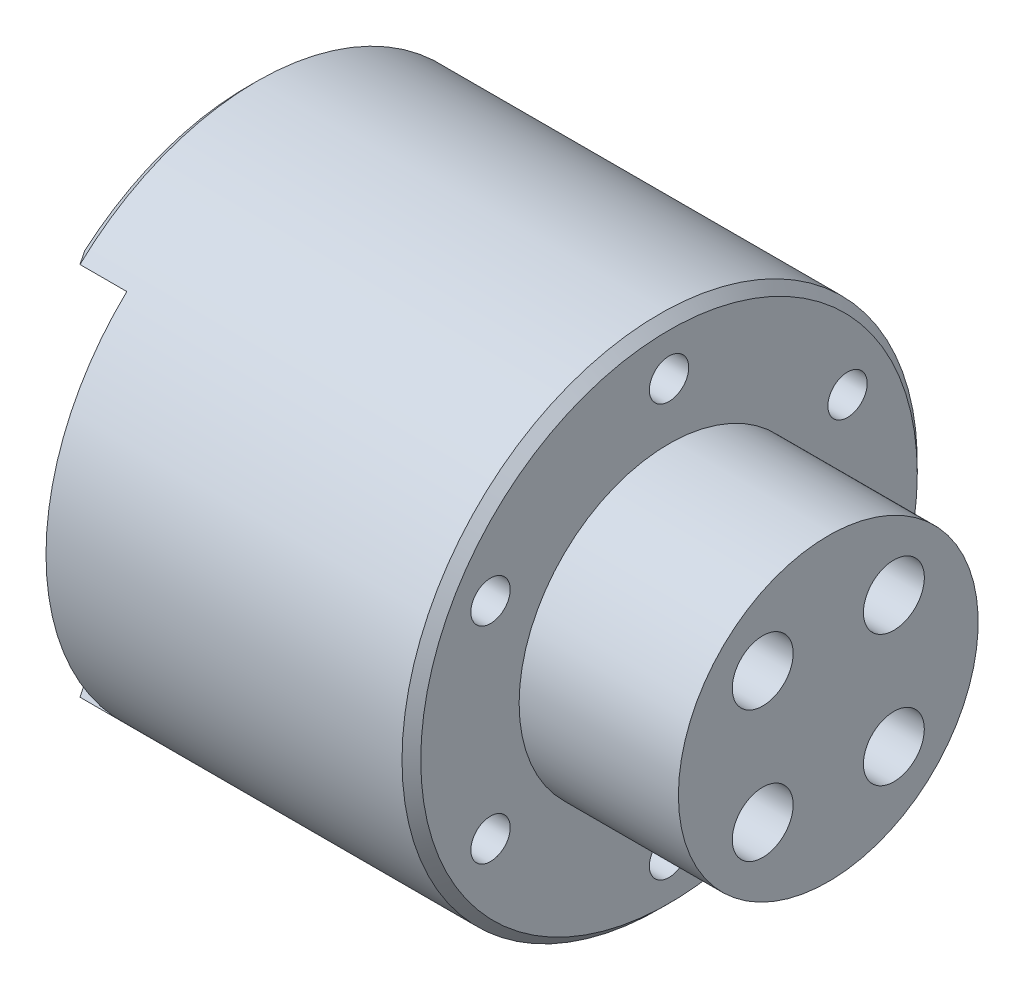
SolidWorks part; units mm, degrees
material "1023 Carbon Steel Sheet (SS)"
ref_plane "Front Plane" through (0, 0, 0) normal (0, 0, 1) x (1, 0, 0)
ref_plane "Top Plane" through (0, 0, 0) normal (0, 1, 0) x (1, 0, 0)
ref_plane "Right Plane" through (0, 0, 0) normal (1, 0, 0) x (0, 0, -1)
sketch "Sketch1" plane through (0, 0, 0) normal (0, 0, 1) x (1, 0, 0)
  line L0 (0, 0) -> (221.0251, 0) construction
  line L1 (55, 0) -> (-55, 0) construction
  line L2 (0, 0) -> (0, 27.5)
  line L3 (0, -55) -> (0, 55) construction
  line L4 (0, 27.5) -> (45, 27.5)
  line L13 (45, 27.5) -> (45, 16)
  line L14 (62, 0) -> (0, 0)
  line L15 (45, 16) -> (62, 16)
  line L16 (62, 16) -> (62, 0)
  dimension "D1" = 45
  dimension "D2" = 55
  dimension "D3" = 32
  dimension "D4" = 17
revolve "Revolve1" add sketch "Sketch1" angle 360 about L0
ref_axis "Axis1" through (45, 0, 0) along (-1, 0, 0)
sketch "Sketch2" plane through (0, 0, 0) normal (-1, 0, 0) x (0, 0, 1)
  line L0 (0, -18.7) -> (0, 18.7) construction
  line L1 (55, 0) -> (-55, 0) construction
  circle A0 centre (-7, 7) radius 3.25
  circle A1 centre (7, 7) radius 3.25
  circle A2 centre (7, -7) radius 3.25
  circle A3 centre (-7, -7) radius 3.25
  dimension "D3" = 6.5
  dimension "D1" = 14
  dimension "D2" = 14
extrude "Cut-Extrude1" cut sketch "Sketch2" against normal through all
sketch "Sketch3" plane through (45, 0, 0) normal (1, 0, 0) x (0, 0, -1)
  line L0 (0, 18.7) -> (0, -18.7) construction
  line L1 (30.25, 0) -> (-30.25, 0) construction
  circle A0 centre (0, 22) radius 2.1
  dimension "D1" = 4.2
  dimension "D2" = 22
extrude "Cut-Extrude2" cut sketch "Sketch3" against normal blind 20
cosmetic thread "Cosmetic Thread5" parameters "D1"=15, "D2"=5
chamfer "Chamfer1" distance 1 angle 45 6 edges at (0, 0, 27.5) (45, 0, 27.5) (0, 7, -3.75) (0, 7, 3.75) (0, -7, 10.25) (0, -7, -10.25)
sketch "Sketch4" plane through (0, 0, 0) normal (-1, 0, 0) x (0, 0, 1)
  line L0 (-18.8746, 20) -> (18.8746, 20)
  line L1 (30.25, 0) -> (-30.25, 0) construction
  line L2 (-18.8746, -20) -> (18.8746, -20)
  circle A0 centre (0, 0) radius 27.5 construction
  arc A1 (-18.8746, 20) -> (-18.8746, -20) centre (0, 0) ccw
  arc A2 (18.8746, -20) -> (18.8746, 20) centre (0, 0) ccw
  dimension "D1" = 40
extrude "Cut-Extrude3" cut sketch "Sketch4" against normal blind 6
pattern_circular "CirPattern1" count 6 every 60 about axis through (62, 0, 0) along (-1, 0, 0) of "Cut-Extrude2"
cosmetic thread "Cosmetic Thread6" parameters "D1"=15, "D2"=5
cosmetic thread "Cosmetic Thread7" parameters "D1"=15, "D2"=5
cosmetic thread "Cosmetic Thread8" parameters "D1"=15, "D2"=5
cosmetic thread "Cosmetic Thread9" parameters "D1"=15, "D2"=5
cosmetic thread "Cosmetic Thread10" parameters "D1"=15, "D2"=5
